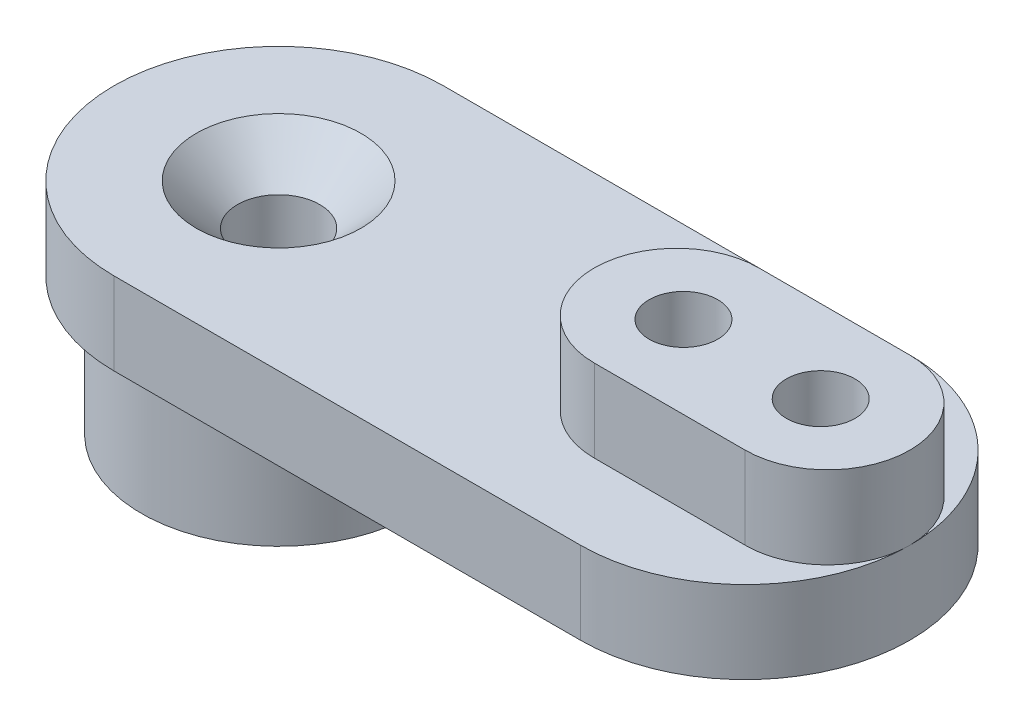
SolidWorks part; units mm, degrees
material "ABS"
ref_plane "Front Plane" through (0, 0, 0) normal (0, 0, 1) x (1, 0, 0)
ref_plane "Top Plane" through (0, 0, 0) normal (0, 1, 0) x (1, 0, 0)
ref_plane "Right Plane" through (0, 0, 0) normal (1, 0, 0) x (0, 0, -1)
sketch "Sketch1" plane through (0, 0, 0) normal (0, 1, 0) x (1, 0, 0)
  line L0 (-8.5, 0) -> (8.5, 0) construction
  line L1 (-8.5, 6) -> (8.5, 6)
  line L2 (-8.5, -6) -> (8.5, -6)
  line L3 (8.5, 0) -> (11.25, 0) construction
  arc A0 (-8.5, 6) -> (-8.5, -6) centre (-8.5, 0) ccw
  arc A1 (8.5, -6) -> (8.5, 6) centre (8.5, 0) ccw
  circle A2 centre (-8.5, 0) radius 1.5
  circle A3 centre (11.25, 0) radius 1.25
  circle A4 centre (6.25, 0) radius 1.25
  point P2 (0, 0)
  dimension "D3" = 2.5
  dimension "D4" = 2.5
  dimension "D5" = 2.75
  dimension "D6" = 5
  dimension "D1" = 12
  dimension "D2" = 17
extrude "Boss-Extrude1" add sketch "Sketch1" along normal blind 3
sketch "Sketch2" plane through (0, 3, 0) normal (0, 1, 0) x (1, 0, 0)
  line L0 (6, 0) -> (11.5, 0) construction
  line L1 (6, 3) -> (11.5, 3)
  line L2 (6, -3) -> (11.5, -3)
  arc A0 (6, 3) -> (6, -3) centre (6, 0) ccw
  arc A1 (11.5, -3) -> (11.5, 3) centre (11.5, 0) ccw
  circle A2 centre (11.25, 0) radius 1.25 construction
  circle A5 centre (6.25, 0) radius 1.25
  circle A6 centre (6.25, 0) radius 1.25
  circle A8 centre (11.25, 0) radius 1.25
  circle A9 centre (11.25, 0) radius 1.25
  point P2 (8.75, 0)
  dimension "D1" = 6
  dimension "D2" = 5.5
  dimension "D3" = 2.5
  dimension "D4" = 0
  dimension "D5" = 0
extrude "Boss-Extrude2" add sketch "Sketch2" along normal blind 3
sketch "Sketch3" plane through (0, 0, 0) normal (0, -1, 0) x (1, 0, 0)
  circle A0 centre (-8.5, 0) radius 5
  circle A1 centre (-8.5, 0) radius 3
  circle M7 centre (-8.5, 0) radius 1.5
  dimension "D1" = 10
  dimension "D2" = 6
extrude "Boss-Extrude3" add sketch "Sketch3" along normal blind 5
extrude "Boss-Extrude4" add sketch "Sketch3<2>" along normal blind 1 contours A1 M7 region at (-11.4151, 0, 0)
sketch "Sketch3<2>" plane through (0, 0, 0) normal (0, -1, 0) x (1, 0, 0) same geometry as "Sketch3"
chamfer "Chamfer1" distance 1.5 angle 45 1 edges at (-8.5, 3, 1.5)
